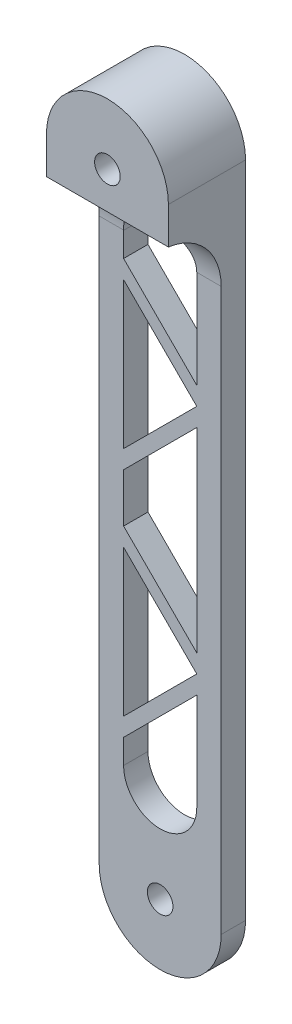
SolidWorks part; units mm, degrees
material "PLA"
ref_plane "Alzado" through (0, 0, 0) normal (0, 0, 1) x (1, 0, 0)
ref_plane "Planta" through (0, 0, 0) normal (0, 1, 0) x (1, 0, 0)
ref_plane "Vista lateral" through (0, 0, 0) normal (1, 0, 0) x (0, 0, -1)
sketch "Croquis1" plane through (0, 0, 0) normal (0, 0, 1) x (1, 0, 0)
  line L0 (0, 54) -> (0, -54) construction
  line L1 (10, 54) -> (10, -54)
  line L2 (-10, 54) -> (-10, -54)
  line L3 (0, 38) -> (0, -38) construction
  line L4 (6, 38) -> (6, -38)
  line L5 (-6, 38) -> (-6, -38)
  line L6 (-10, -47.95) -> (10, -47.95)
  line L7 (0, 51.9) -> (0, 44) construction
  line L8 (-10, 47.95) -> (10, 47.95)
  line L9 (0, -51.9) -> (0, -44) construction
  line L10 (-10, 0) -> (10, 0) construction
  line L11 (6, -19) -> (-6, -31)
  line L12 (-6, -34) -> (6, -22)
  line L13 (0, -38) -> (0, 0) construction
  line L14 (-6, -19) -> (6, -19) construction
  line L15 (-6, -4) -> (6, -16)
  line L16 (6, -19) -> (-6, -7)
  line L17 (-6, 4) -> (6, 16)
  line L18 (6, 19) -> (-6, 7)
  line L19 (6, 19) -> (-6, 31)
  line L20 (-6, 34) -> (6, 22)
  arc A0 (10, 54) -> (-10, 54) centre (0, 54) ccw
  arc A1 (-10, -54) -> (10, -54) centre (0, -54) ccw
  circle A2 centre (0, 54) radius 2.1
  circle A3 centre (0, -54) radius 2.1
  arc A4 (6, 38) -> (-6, 38) centre (0, 38) ccw
  arc A5 (-6, -38) -> (6, -38) centre (0, -38) ccw
  point P2 (0, 0)
  point P14 (0, 0)
  point P23 (0, 47.95)
  point P28 (0, -47.95)
  point P39 (0, -19)
  point P40 (0, -17.5931)
  point P41 (6, -19.3969)
  dimension "D1" = 4.2
  dimension "D2" = 20
  dimension "D3" = 108
  dimension "D4" = 4
  dimension "D5" = 16
  dimension "D6" = 135
  dimension "D7" = 3
extrude "Saliente-Extruir1" add sketch "Croquis1" along normal blind 4 contours L1 A0 L2 L8 A2 | L2 A1 L1 L8 A5 L5 A4 L4 A3 | L5 L12 L4 L11 | L16 L4 L15 L5 | L4 L18 L5 L17 | L20 L5 L19 L4 | L2 A1 L1 A0 | A3 | L5 A5 L4 A4 | A2 region at (9.7436, 50.975, 0) region at (9.0204, 0, 0) region at (0, 26.5, 0) region at (0, 11.5, 0) region at (0, -11.5, 0) region at (0, -26.5, 0)
extrude "Saliente-Extruir3" add sketch "Croquis1<6>" along normal up to surface (12.65 mm away) contours L1 A0 L2 L8 A2 region at (9.7436, 50.975, 0) up to face at (0, 34.5, 0)
sketch "Croquis1<6>" plane through (0, 0, 0) normal (0, 0, 1) x (1, 0, 0) same geometry as "Croquis1"
fillet "Redondeo1" radius 10 1 edges at (0, 47.95, 4)
